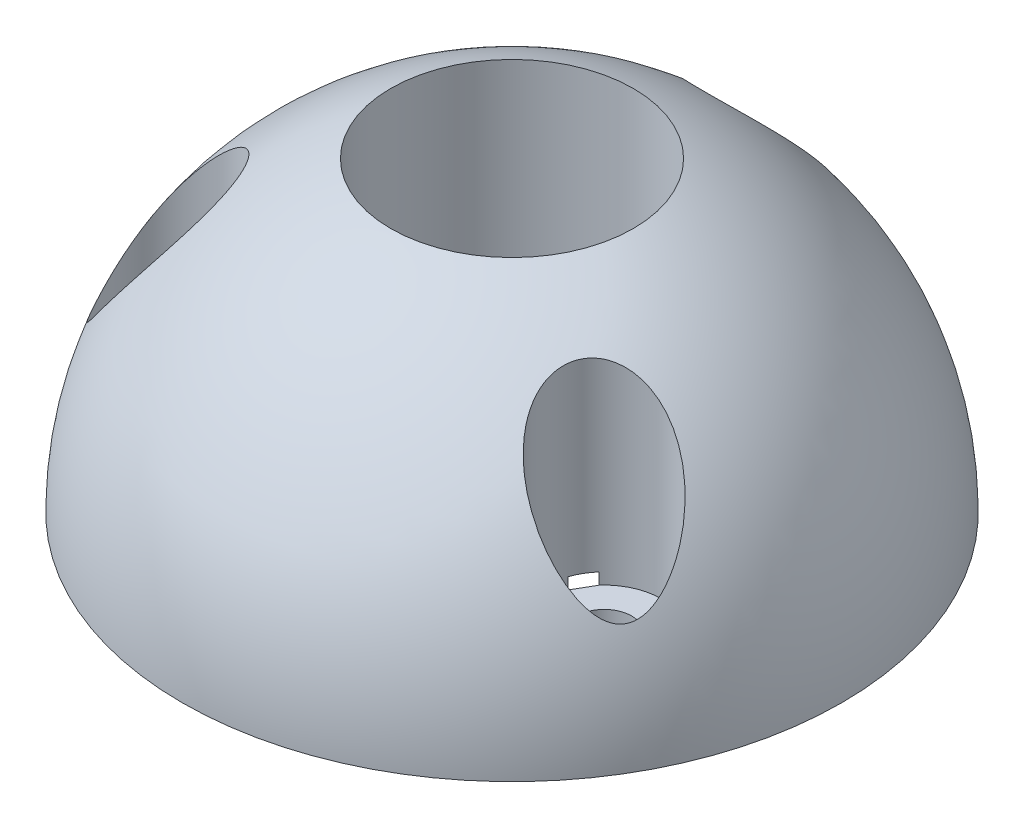
SolidWorks part; units mm, degrees
ref_plane "Front Plane" through (0, 0, 0) normal (0, 0, 1) x (1, 0, 0)
ref_plane "Top Plane" through (0, 0, 0) normal (0, 1, 0) x (1, 0, 0)
ref_plane "Right Plane" through (0, 0, 0) normal (1, 0, 0) x (0, 0, -1)
sketch "Sketch1" plane through (0, 0, 0) normal (0, 0, 1) x (1, 0, 0)
  line L0 (-14.4, 0) -> (14.4, 0)
  line L1 (0, -1000) -> (0, 49000) construction
  arc A0 (14.4, 0) -> (-14.4, 0) centre (0, 0) ccw
  dimension "D1" = 14.4
revolve "Revolve1" add sketch "Sketch1" angle 360 about L1 region at (-6.1115, 6.1115, 0)
sketch "Sketch2" plane through (0, 0, 0) normal (0, -1, 0) x (1, 0, 0)
  line L1 (4.9363, -8.55) -> (9.8727, 0)
  line L2 (9.8727, 0) -> (4.9363, 8.55)
  line L3 (4.9363, 8.55) -> (-4.9363, 8.55)
  line L4 (-4.9363, 8.55) -> (-9.8727, 0)
  line L5 (-9.8727, 0) -> (-4.9363, -8.55)
  line L6 (-4.9363, -8.55) -> (4.9363, -8.55)
  circle A0 centre (0, 0) radius 8.55 construction
  dimension "D1" = 17.1
extrude "Cut-Extrude2" cut sketch "Sketch2" against normal blind 3.5
sketch "Sketch3" plane through (0, 3.5, 0) normal (0, -1, 0) x (1, 0, 0)
  line L0 (-4.9363, 8.55) -> (-9.8727, 0) construction
  line L1 (3.7816, -6.55) -> (7.5633, 0)
  line L2 (7.5633, 0) -> (3.7816, 6.55)
  line L3 (3.7816, 6.55) -> (-3.7816, 6.55)
  line L4 (-3.7816, 6.55) -> (-7.5633, 0)
  line L5 (-7.5633, 0) -> (-3.7816, -6.55)
  line L6 (-3.7816, -6.55) -> (3.7816, -6.55)
  circle A0 centre (0, 0) radius 5.3
  circle A1 centre (0, 0) radius 6.55 construction
  dimension "D1" = 10.6
  dimension "D2" = 2
sketch "Sketch7" plane through (0, 0, 0) normal (0, -1, 0) x (1, 0, 0)
  line L0 (866.0254, -500) -> (-42435.2448, 24500) construction
  line L1 (-707.1068, -707.1068) -> (34648.2323, 34648.2323) construction
  line L2 (0, -1000) -> (0, 49000) construction
  circle A0 centre (-9.5263, 5.5) radius 1.2
  circle A1 centre (9.5263, 5.5) radius 1.2
  circle A2 centre (0, -11) radius 1.2
  point P16 (0, 0)
  dimension "D1" = 2.4
  dimension "D3" = 11
  dimension "D4" = 60
  dimension "D2" = 3
extrude "Cut-Extrude6" cut sketch "Sketch7" against normal blind 7
extrude "Cut-Extrude7" cut sketch "Sketch3" against normal through all contours A0 region at (0, 3.5, 0)
sketch "Sketch8" plane through (0, 0, 0) normal (0, 1, 0) x (1, 0, 0)
  circle A3 centre (-9.5263, -5.5) radius 2.5
  circle A4 centre (0, 11) radius 2.5
  circle A5 centre (9.5263, -5.5) radius 2.5
  point P9 (0, 0)
  point P12 (0, 0)
  dimension "D2" = 3
  dimension "D1" = 5
extrude "Cut-Extrude8" cut sketch "Sketch8" along normal through all from offset 3
